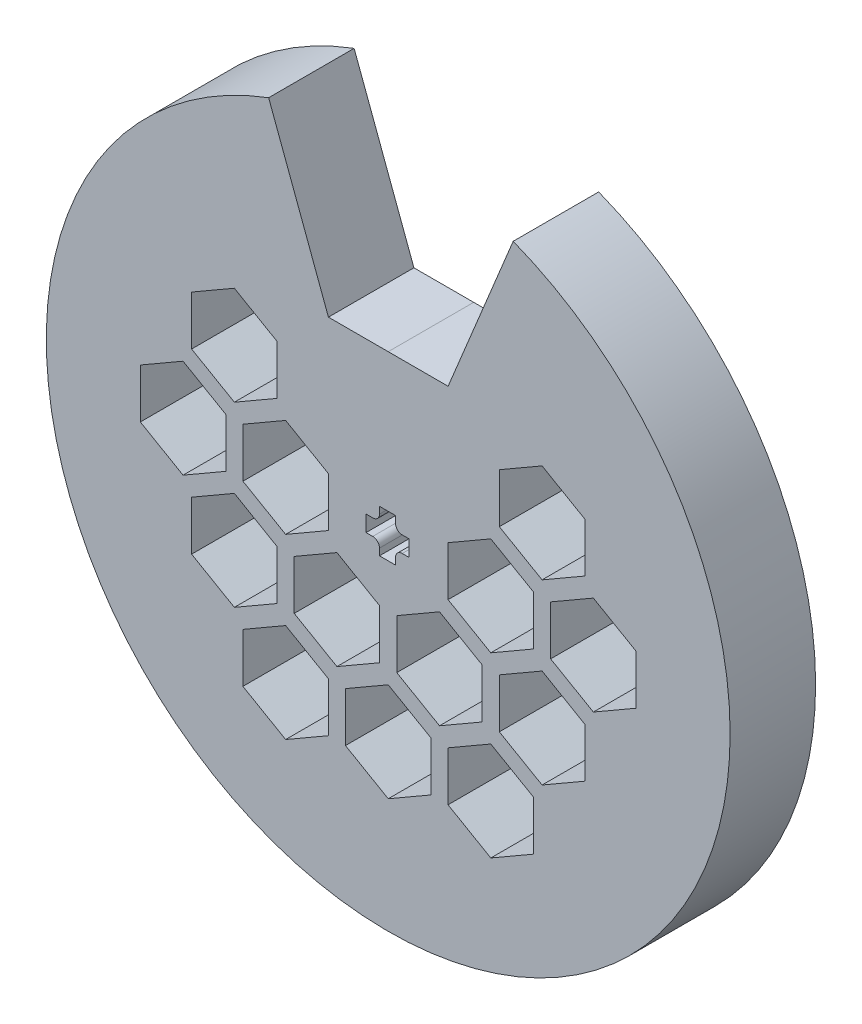
SolidWorks part; units mm, degrees
note: The reader was unsure of these and kept them because the rebuilt part matched: shared geometry of "Sketch1<10>", "Sketch1<11>", "Sketch1<13>".
ref_plane "Front Plane" through (0, 0, 0) normal (0, 0, 1) x (1, 0, 0)
ref_plane "Top Plane" through (0, 0, 0) normal (0, 1, 0) x (1, 0, 0)
ref_plane "Right Plane" through (0, 0, 0) normal (1, 0, 0) x (0, 0, -1)
sketch "Sketch1" plane through (0, 0, 0) normal (0, 0, 1) x (1, 0, 0)
  line L0 (0, 6.9282) -> (-6, 3.4641)
  line L2 (0, 18.7372) -> (7.0059, 18.7372)
  line L4 (0, 18.7372) -> (-6.9941, 18.7372)
  line L5 (7.0059, 18.7372) -> (14.6207, 37.2322)
  line L7 (-6.9941, 18.7372) -> (-13.9882, 37.4744)
  line L8 (5, 2.8868) -> (0, 5.7735)
  line L9 (0, 5.7735) -> (-5, 2.8868)
  line L10 (-5, 2.8868) -> (-5, -2.8868)
  line L11 (0.8537, -2.4576) -> (-1.0206, -2.4576)
  line L12 (-1.0206, -2.4576) -> (-1.0206, -1.6727)
  line L13 (-1.8107, -0.8852) -> (-2.5903, -0.8878)
  line L14 (-2.5903, -0.8878) -> (-2.5903, 0.9917)
  line L15 (-2.5903, 0.9917) -> (-1.8028, 0.9917)
  line L16 (-1.0153, 1.7792) -> (-1.0153, 2.5614)
  line L17 (-1.0153, 2.5614) -> (0.8589, 2.5614)
  line L18 (0.8589, 2.5614) -> (0.8589, 1.7766)
  line L19 (1.6491, 0.9891) -> (2.4287, 0.9917)
  line L20 (2.4287, 0.9917) -> (2.4287, -0.8878)
  line L21 (2.4287, -0.8878) -> (1.6412, -0.8878)
  line L22 (0.8537, -1.6753) -> (0.8537, -2.4576)
  line L35 (-5, -2.8868) -> (0, -5.7735)
  line L36 (0, -5.7735) -> (5, -2.8868)
  line L37 (5, -2.8868) -> (5, 2.8868)
  line L38 (-6, 3.4641) -> (-6, -3.4641)
  line L40 (0, -6.9282) -> (6, -3.4641)
  line L41 (6, -3.4641) -> (6, 3.4641)
  line L42 (6, 3.4641) -> (0, 6.9282)
  line L43 (12, 6.9282) -> (6, 3.4641)
  line L46 (12, -6.9282) -> (18, -3.4641)
  line L47 (18, -3.4641) -> (18, 3.4641)
  line L48 (18, 3.4641) -> (12, 6.9282)
  line L49 (17, 2.8868) -> (12, 5.7735)
  line L50 (12, 5.7735) -> (7, 2.8868)
  line L51 (7, 2.8868) -> (7, -2.8868)
  line L52 (7, -2.8868) -> (12, -5.7735)
  line L53 (12, -5.7735) -> (17, -2.8868)
  line L54 (17, -2.8868) -> (17, 2.8868)
  line L58 (24, -6.9282) -> (30, -3.4641)
  line L59 (30, -3.4641) -> (30, 3.4641)
  line L60 (30, 3.4641) -> (24, 6.9282)
  line L61 (29, 2.8868) -> (24, 5.7735)
  line L62 (24, 5.7735) -> (19, 2.8868)
  line L63 (19, 2.8868) -> (19, -2.8868)
  line L64 (19, -2.8868) -> (24, -5.7735)
  line L65 (24, -5.7735) -> (29, -2.8868)
  line L66 (29, -2.8868) -> (29, 2.8868)
  line L69 (30, -3.4641) -> (34.4737, -6.047)
  line L74 (34.6425, 4.9897) -> (31, 2.8868)
  line L75 (31, 2.8868) -> (31, -2.8868)
  line L76 (31, -2.8868) -> (34.6425, -4.9897)
  line L79 (-7, 2.8868) -> (-12, 5.7735)
  line L80 (-12, 5.7735) -> (-17, 2.8868)
  line L81 (-17, 2.8868) -> (-17, -2.8868)
  line L82 (-17, -2.8868) -> (-12, -5.7735)
  line L83 (-12, -5.7735) -> (-7, -2.8868)
  line L84 (-7, -2.8868) -> (-7, 2.8868)
  line L85 (-12, 6.9282) -> (-18, 3.4641)
  line L86 (-18, 3.4641) -> (-18, -3.4641)
  line L91 (-19, 2.8868) -> (-24, 5.7735)
  line L92 (-24, 5.7735) -> (-29, 2.8868)
  line L93 (-29, 2.8868) -> (-29, -2.8868)
  line L94 (-29, -2.8868) -> (-24, -5.7735)
  line L95 (-24, -5.7735) -> (-19, -2.8868)
  line L96 (-19, -2.8868) -> (-19, 2.8868)
  line L97 (-24, 6.9282) -> (-30, 3.4641)
  line L98 (-30, 3.4641) -> (-30, -3.4641)
  line L103 (-31, 2.8868) -> (-34.6425, 4.9897)
  line L107 (-34.6425, -4.9897) -> (-31, -2.8868)
  line L108 (-31, -2.8868) -> (-31, 2.8868)
  line L114 (-30, 3.4641) -> (-34.4737, 6.047)
  line L115 (0, 6.9282) -> (0, 13.7372)
  line L116 (-10.2065, 13.7372) -> (-11, 13.2791)
  line L119 (24, 6.9282) -> (24, 13.8564)
  line L120 (11, 13.2791) -> (10.2065, 13.7372)
  line L121 (11, 7.5056) -> (11, 13.2791)
  line L122 (-10.7735, 14.5645) -> (-12, 13.8564)
  line L123 (-13, 13.2791) -> (-18, 16.1658)
  line L124 (-24, 6.9282) -> (-18, 3.4641)
  line L125 (-30, 16.1658) -> (-31.4706, 15.3168)
  line L126 (-30, 4.6188) -> (-25, 7.5056)
  line L128 (30.6125, 16.9669) -> (30, 17.3205)
  line L129 (23, 7.5056) -> (23, 13.2791)
  line L131 (-1, 13.2791) -> (-1.7935, 13.7372)
  line L134 (24, 13.8564) -> (18, 17.3205)
  line L135 (12, 6.9282) -> (12, 13.8564)
  line L136 (-11, 13.2791) -> (-11, 7.5056)
  line L137 (-11, 7.5056) -> (-6, 4.6188)
  line L139 (-24, 6.9282) -> (-24, 13.8564)
  line L140 (30, 4.6188) -> (34.275, 7.087)
  line L143 (18, 4.6188) -> (23, 7.5056)
  line L144 (-13, 7.5056) -> (-13, 13.2791)
  line L145 (30, 16.1658) -> (25, 13.2791)
  line L146 (30, 17.3205) -> (24, 13.8564)
  line L148 (18, 16.1658) -> (13, 13.2791)
  line L151 (25, 7.5056) -> (30, 4.6188)
  line L153 (13, 13.2791) -> (13, 7.5056)
  line L154 (-23, 13.2791) -> (-23, 7.5056)
  line L155 (31.4706, 15.3168) -> (30, 16.1658)
  line L157 (-12, 13.8564) -> (-12, 6.9282)
  line L158 (-30, 17.3205) -> (-30.6125, 16.9669)
  line L159 (-34.275, 7.087) -> (-30, 4.6188)
  line L161 (18, 17.3205) -> (12, 13.8564)
  line L162 (18, 3.4641) -> (24, 6.9282)
  line L163 (1, 7.5056) -> (6, 4.6188)
  line L164 (-12, 6.9282) -> (-6, 3.4641)
  line L165 (-6, 4.6188) -> (-1, 7.5056)
  line L166 (-18, 4.6188) -> (-13, 7.5056)
  line L169 (-25, 13.2791) -> (-30, 16.1658)
  line L171 (23, 13.2791) -> (18, 16.1658)
  line L174 (-18, 16.1658) -> (-23, 13.2791)
  line L177 (12, 13.8564) -> (10.7102, 14.6011)
  line L178 (-23, 7.5056) -> (-18, 4.6188)
  line L181 (-1, 7.5056) -> (-1, 13.2791)
  line L183 (25, 13.2791) -> (25, 7.5056)
  line L184 (30, 3.4641) -> (34.4737, 6.047)
  line L187 (13, 7.5056) -> (18, 4.6188)
  line L188 (6, 4.6188) -> (11, 7.5056)
  line L190 (-18, 17.3205) -> (-24, 13.8564)
  line L193 (1.7935, 13.7372) -> (1, 13.2791)
  line L194 (1, 13.2791) -> (1, 7.5056)
  line L195 (-24, 13.8564) -> (-30, 17.3205)
  line L196 (-25, 7.5056) -> (-25, 13.2791)
  line L199 (-19, 17.8979) -> (-19, 23.6714)
  line L200 (-17, 17.8979) -> (-12, 15.0111)
  line L201 (-15.0287, 25.9642) -> (-18, 24.2487)
  line L203 (-12, 15.0111) -> (-11.1281, 15.5145)
  line L205 (22.4737, 26.8316) -> (18, 24.2487)
  line L208 (18, 17.3205) -> (18, 24.2487)
  line L215 (24, 15.0111) -> (29, 17.8979)
  line L218 (-24, 15.0111) -> (-19, 17.8979)
  line L237 (-29, 17.8979) -> (-24, 15.0111)
  line L238 (-17, 23.6714) -> (-17, 17.8979)
  line L241 (19, 17.8979) -> (24, 15.0111)
  line L242 (30, 17.3205) -> (30, 18.0278)
  line L243 (-30, 17.3205) -> (-30, 18.0278)
  line L246 (12, 15.0111) -> (17, 17.8979)
  line L251 (-19, 23.6714) -> (-23.275, 26.1395)
  line L254 (-29, 19.5959) -> (-29, 17.8979)
  line L256 (17, 17.8979) -> (17, 23.6714)
  line L258 (29, 17.8979) -> (29, 19.5959)
  line L259 (-18, 24.2487) -> (-18, 17.3205)
  line L263 (17, 23.6714) -> (14.9354, 24.8634)
  line L266 (-14.6741, 25.0142) -> (-17, 23.6714)
  line L270 (11.0943, 15.534) -> (12, 15.0111)
  line L271 (23.275, 26.1395) -> (19, 23.6714)
  line L274 (-18, 17.3205) -> (-12, 13.8564)
  line L276 (18, 24.2487) -> (15.3195, 25.7963)
  line L277 (19, 23.6714) -> (19, 17.8979)
  line L283 (-13, -13.2791) -> (-13, -7.5056)
  line L284 (-11, -13.2791) -> (-6, -16.1658)
  line L285 (-6, -3.4641) -> (-12, -6.9282)
  line L286 (-18, -17.3205) -> (-12, -13.8564)
  line L287 (-6, -16.1658) -> (-1, -13.2791)
  line L288 (34.275, -7.087) -> (30, -4.6188)
  line L291 (6, -16.1658) -> (11, -13.2791)
  line L292 (24, -13.8564) -> (24, -6.9282)
  line L295 (-30, -4.6188) -> (-34.275, -7.087)
  line L296 (-18, -3.4641) -> (-24, -6.9282)
  line L297 (-18, -4.6188) -> (-23, -7.5056)
  line L299 (30, -16.1658) -> (31.4706, -15.3168)
  line L302 (-18, -16.1658) -> (-13, -13.2791)
  line L303 (-1, -7.5056) -> (-6, -4.6188)
  line L304 (0, -13.8564) -> (0, -6.9282)
  line L306 (1, -7.5056) -> (1, -13.2791)
  line L308 (-30, -16.1658) -> (-25, -13.2791)
  line L309 (-25, -13.2791) -> (-25, -7.5056)
  line L310 (11, -13.2791) -> (11, -7.5056)
  line L311 (6, -17.3205) -> (12, -13.8564)
  line L313 (-24, -6.9282) -> (-30, -3.4641)
  line L315 (-12, -6.9282) -> (-18, -3.4641)
  line L320 (-30.6125, -16.9669) -> (-30, -17.3205)
  line L321 (-23, -13.2791) -> (-18, -16.1658)
  line L322 (-11, -7.5056) -> (-11, -13.2791)
  line L323 (-1, -13.2791) -> (-1, -7.5056)
  line L324 (13, -7.5056) -> (13, -13.2791)
  line L325 (25, -13.2791) -> (30, -16.1658)
  line L327 (-24, -13.8564) -> (-24, -6.9282)
  line L328 (-6, -17.3205) -> (0, -13.8564)
  line L330 (18, -16.1658) -> (23, -13.2791)
  line L334 (-25, -7.5056) -> (-30, -4.6188)
  line L335 (-13, -7.5056) -> (-18, -4.6188)
  line L338 (-23, -7.5056) -> (-23, -13.2791)
  line L339 (6, -4.6188) -> (1, -7.5056)
  line L340 (23, -13.2791) -> (23, -7.5056)
  line L341 (18, -17.3205) -> (24, -13.8564)
  line L343 (-12, -6.9282) -> (-12, -13.8564)
  line L344 (11, -7.5056) -> (6, -4.6188)
  line L345 (1, -13.2791) -> (6, -16.1658)
  line L347 (23, -7.5056) -> (18, -4.6188)
  line L350 (-6, -4.6188) -> (-11, -7.5056)
  line L351 (0, -6.9282) -> (-6, -3.4641)
  line L352 (12, -13.8564) -> (12, -6.9282)
  line L353 (18, -4.6188) -> (13, -7.5056)
  line L354 (13, -13.2791) -> (18, -16.1658)
  line L355 (30, -4.6188) -> (25, -7.5056)
  line L356 (-31.4706, -15.3168) -> (-30, -16.1658)
  line L357 (-30, -3.4641) -> (-34.4737, -6.047)
  line L359 (12, -6.9282) -> (6, -3.4641)
  line L360 (24, -6.9282) -> (18, -3.4641)
  line L361 (25, -7.5056) -> (25, -13.2791)
  line L366 (30, -17.3205) -> (30.6125, -16.9669)
  line L367 (-19, -23.6714) -> (-19, -17.8979)
  line L368 (-17, -23.6714) -> (-12, -26.5581)
  line L370 (-22.4737, -26.8316) -> (-18, -24.2487)
  line L371 (-12, -26.5581) -> (-7, -23.6714)
  line L372 (29, -17.8979) -> (24, -15.0111)
  line L375 (0, -26.5581) -> (5, -23.6714)
  line L376 (18, -24.2487) -> (18, -17.3205)
  line L380 (-24, -13.8564) -> (-30, -17.3205)
  line L381 (-24, -15.0111) -> (-29, -17.8979)
  line L386 (-23.275, -26.1395) -> (-19, -23.6714)
  line L387 (-7, -17.8979) -> (-12, -15.0111)
  line L390 (-5, -17.8979) -> (-5, -23.6714)
  line L394 (5, -23.6714) -> (5, -17.8979)
  line L395 (0, -27.7128) -> (6, -24.2487)
  line L399 (-18, -17.3205) -> (-24, -13.8564)
  line L406 (-17, -17.8979) -> (-17, -23.6714)
  line L407 (-7, -23.6714) -> (-7, -17.8979)
  line L408 (7, -17.8979) -> (7, -23.6714)
  line L409 (19, -23.6714) -> (23.275, -26.1395)
  line L410 (30, -18.0278) -> (30, -17.3205)
  line L412 (-12, -27.7128) -> (-6, -24.2487)
  line L413 (-6, -17.3205) -> (-6, -24.2487)
  line L414 (12, -26.5581) -> (17, -23.6714)
  line L419 (-19, -17.8979) -> (-24, -15.0111)
  line L422 (-29, -17.8979) -> (-29, -19.5959)
  line L423 (0, -15.0111) -> (-5, -17.8979)
  line L424 (17, -23.6714) -> (17, -17.8979)
  line L425 (12, -27.7128) -> (18, -24.2487)
  line L426 (29, -19.5959) -> (29, -17.8979)
  line L427 (-18, -17.3205) -> (-18, -24.2487)
  line L428 (5, -17.8979) -> (0, -15.0111)
  line L429 (-5, -23.6714) -> (0, -26.5581)
  line L431 (17, -17.8979) -> (12, -15.0111)
  line L432 (30, -17.3205) -> (24, -13.8564)
  line L434 (-12, -15.0111) -> (-17, -17.8979)
  line L435 (-6, -17.3205) -> (-12, -13.8564)
  line L436 (6, -24.2487) -> (6, -17.3205)
  line L437 (12, -15.0111) -> (7, -17.8979)
  line L438 (7, -23.6714) -> (12, -26.5581)
  line L439 (24, -15.0111) -> (19, -17.8979)
  line L443 (6, -17.3205) -> (0, -13.8564)
  line L444 (18, -17.3205) -> (12, -13.8564)
  line L445 (19, -17.8979) -> (19, -23.6714)
  line L448 (-30, -17.3205) -> (-30, -18.0278)
  line L456 (21.6425, -27.5064) -> (18, -25.4034)
  line L459 (-2.4706, -34.9127) -> (-1, -34.0637)
  line L460 (12, -32.8786) -> (12, -27.7128)
  line L471 (-13, -28.2902) -> (-18, -25.4034)
  line L474 (-11, -28.2902) -> (-11, -33.2265)
  line L478 (-1, -34.0637) -> (-1, -28.2902)
  line L479 (-0.6125, -34.9946) -> (0, -34.641)
  line L491 (-13, -32.4962) -> (-13, -28.2902)
  line L492 (1, -28.2902) -> (1, -34.0637)
  line L497 (-12, -27.7128) -> (-12, -32.8786)
  line L507 (-6, -25.4034) -> (-11, -28.2902)
  line L508 (11, -33.2265) -> (11, -28.2902)
  line L512 (-1, -28.2902) -> (-6, -25.4034)
  line L515 (11, -28.2902) -> (6, -25.4034)
  line L516 (22.4737, -26.8316) -> (18, -24.2487)
  line L518 (-18, -25.4034) -> (-21.6425, -27.5064)
  line L519 (-12, -27.7128) -> (-18, -24.2487)
  line L520 (0, -34.641) -> (0, -27.7128)
  line L521 (6, -25.4034) -> (1, -28.2902)
  line L522 (1, -34.0637) -> (2.4706, -34.9127)
  line L523 (18, -25.4034) -> (13, -28.2902)
  line L527 (0, -27.7128) -> (-6, -24.2487)
  line L528 (12, -27.7128) -> (6, -24.2487)
  line L529 (13, -28.2902) -> (13, -32.4962)
  line L533 (0, -34.641) -> (0.6125, -34.9946)
  line L536 (-21.6425, 27.5064) -> (-18, 25.4034)
  line L539 (-18, 25.4034) -> (-15.3833, 26.9142)
  line L551 (18, 25.4034) -> (21.6425, 27.5064)
  line L577 (15.7036, 26.7292) -> (18, 25.4034)
  line L610 (-22.4737, 26.8316) -> (-18, 24.2487)
  line L619 (42, 3.4641) -> (39.7128, 4.7846) [skipped]
  line L620 (42, -3.4641) -> (42, 3.4641) [skipped]
  line L621 (41, -2.8868) -> (41, 2.8868) [skipped]
  line L622 (41, 2.8868) -> (39.8417, 3.5555) [skipped]
  line L623 (-42, 3.4641) -> (-42, -3.4641) [skipped]
  line L624 (-41, 2.8868) -> (-41, -2.8868) [skipped]
  line L625 (-36, 5.7735) -> (-39.8417, 3.5555) [skipped]
  line L626 (-36, 6.9282) -> (-39.7128, 4.7846) [skipped]
  line L627 (-39.8417, -3.5555) -> (-36, -5.7735) [skipped]
  line L629 (36, -5.7735) -> (39.8417, -3.5555) [skipped]
  line L630 (36, -6.9282) -> (39.7128, -4.7846) [skipped]
  line L631 (10.3545, 13.7372) -> (17.2396, 30.4598)
  line L632 (0, 13.7372) -> (10.3545, 13.7372)
  line L633 (0, 13.7372) -> (-10.4647, 13.7372)
  line L634 (-10.4647, 13.7372) -> (-16.7984, 30.7053)
  line L635 (-18.5628, 35.432) -> (-18.6725, 35.7259)
  line L636 (-10.4647, 13.7372) -> (-18.6725, 35.7259) construction
  line L637 (19.1561, 35.1147) -> (19.2442, 35.3286)
  line L638 (10.3545, 13.7372) -> (19.2442, 35.3286) construction
  line L639 (-24, -6.9282) -> (-18, -3.4641) [skipped]
  line L640 (-6, -3.4641) -> (-6, 3.4641) [skipped]
  line L641 (-18, 3.4641) -> (-24, 6.9282) [skipped]
  line L642 (-6, -3.4641) -> (0, -6.9282) construction
  line L643 (24, 6.9282) -> (18, 3.4641) [skipped]
  line L644 (6, 3.4641) -> (6, -3.4641) [skipped]
  line L645 (-12, -6.9282) -> (-6, -3.4641) [skipped]
  line L646 (-6, 3.4641) -> (-12, 6.9282) [skipped]
  line L647 (34.4737, 6.047) -> (30, 3.4641) [skipped]
  line L648 (18, 3.4641) -> (18, -3.4641) [skipped]
  line L649 (30, 3.4641) -> (30, -3.4641) [skipped]
  line L650 (-34.4737, -6.047) -> (-30, -3.4641) [skipped]
  line L651 (-18, -3.4641) -> (-18, 3.4641) [skipped]
  line L652 (-30, -3.4641) -> (-30, 3.4641) [skipped]
  circle A0 centre (0, 0) radius 40
  arc A1 (-1.0206, -1.6727) -> (-1.8107, -0.8852) centre (-1.8081, -1.6727) ccw
  arc A2 (-1.8028, 0.9917) -> (-1.0153, 1.7792) centre (-1.8028, 1.7792) ccw
  arc A3 (0.8589, 1.7766) -> (1.6491, 0.9891) centre (1.6464, 1.7766) ccw
  arc A4 (1.6412, -0.8878) -> (0.8537, -1.6753) centre (1.6412, -1.6753) ccw
  arc A9 (-16.7984, 30.7053) -> (17.2396, 30.4598) centre (0, 0) ccw
  circle A10 centre (0, 0) radius 5 construction
  point P9 (-35.9976, 27.8852)
  dimension "D1" = 80
  dimension "D2" = 1
  dimension "D4" = 4
  dimension "D5" = 4
  dimension "D6" = 5
extrude "Boss-Extrude1" add sketch "Sketch1" along normal blind 10 contours A0
extrude "Cut-Extrude8" cut sketch "Sketch1<10>" along normal blind 99 contours L66 L61 L62 L63 L64 L65 | L54 L49 L50 L51 L52 L53 | L344 L339 L306 L345 L291 L310 | L353 L324 L354 L330 L340 L347 | L437 L408 L438 L414 L424 L431 | L428 L423 L390 L429 L375 L394 | L323 L303 L350 L322 L284 L287 | L83 L84 L79 L80 L81 L82 | L387 L434 L406 L368 L371 L407 | L302 L283 L335 L297 L338 L321 | L95 L96 L91 L92 L93 L94 | L166 L144 L123 L174 L154 L178 | L187 L143 L129 L171 L148 L153
sketch "Sketch1<10>" plane through (0, 0, 0) normal (0, 0, 1) x (1, 0, 0) same geometry as "Sketch1"
extrude "Cut-Extrude9" cut sketch "Sketch1<11>" against normal through all and the other way through all contours L7 L4 L2 L5
sketch "Sketch1<11>" plane through (0, 0, 0) normal (0, 0, 1) x (1, 0, 0) same geometry as "Sketch1"
extrude "Cut-Extrude10" cut sketch "Sketch1<13>" along normal blind 23 and the other way through all contours L13 L14 L15 A2 L16 L17 L18 A3 L19 L20 L21 A4 L22 L11 L12 A1
sketch "Sketch1<13>" plane through (0, 0, 0) normal (0, 0, 1) x (1, 0, 0) same geometry as "Sketch1"
